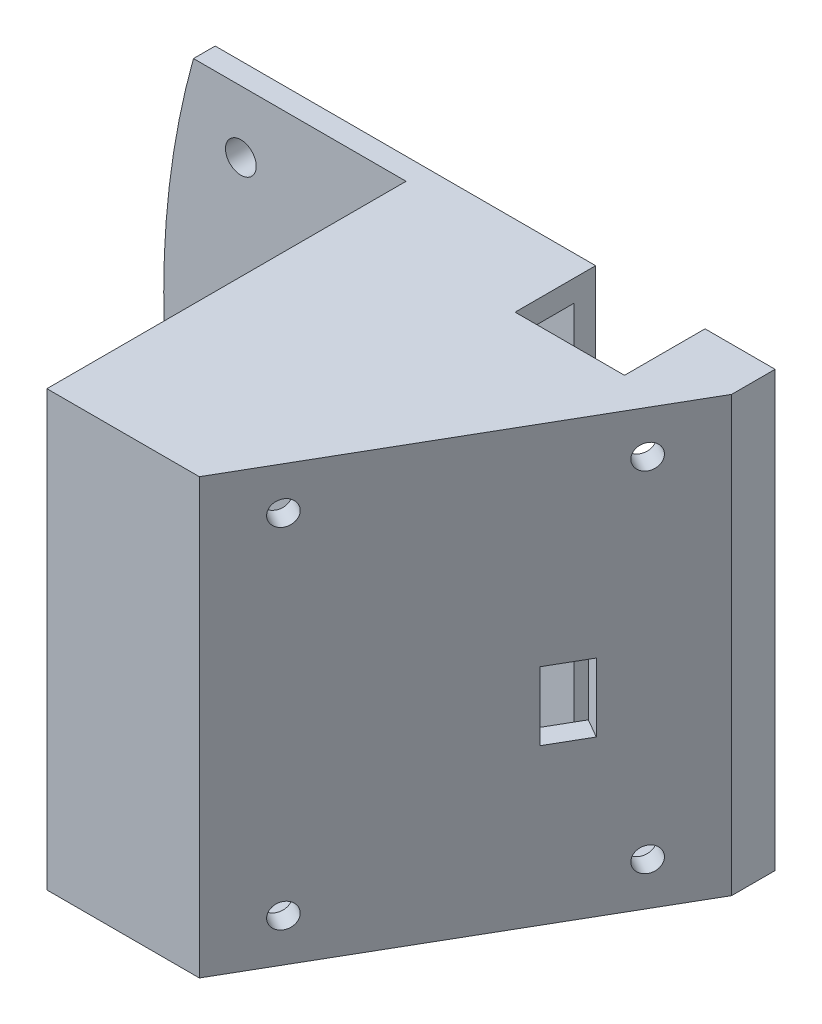
SolidWorks part; units mm, degrees
ref_plane "Front Plane" through (0, 0, 0) normal (0, 0, 1) x (1, 0, 0)
ref_plane "Top Plane" through (0, 0, 0) normal (0, 1, 0) x (1, 0, 0)
ref_plane "Right Plane" through (0, 0, 0) normal (1, 0, 0) x (0, 0, -1)
sketch "Sketch1" plane through (0, 0, 0) normal (0, 0, 1) x (1, 0, 0)
  line L0 (-113.6478, 31.75) -> (-31.75, 31.75)
  line L1 (-31.75, 31.75) -> (-31.75, -31.75)
  line L2 (-31.75, -31.75) -> (-113.6478, -31.75)
  circle A0 centre (-106.7159, 22.6832) radius 2.2479 construction
  circle A1 centre (-109.1, 0) radius 2.2479 construction
  circle A2 centre (-106.7159, -22.6832) radius 2.2479 construction
  circle A3 centre (-106.7159, 22.6832) radius 2.2479
  circle A4 centre (-109.1, 0) radius 2.2479
  circle A5 centre (-106.7159, -22.6832) radius 2.2479
  arc A6 (69.85, 95.1045) -> (69.85, -95.1045) centre (0, 0) ccw construction
  arc A7 (69.85, 95.1045) -> (69.85, -95.1045) centre (0, 0) ccw
  dimension "D1" = 31.75
  dimension "D4" = 63.5
sketch "Sketch5" plane through (0, 0, 0) normal (0, 1, 0) x (1, 0, 0)
  line L2 (-31.75, 0) -> (-31.75, -6.35)
  line L3 (-31.75, -6.35) -> (-60.25, -55.7134)
  line L4 (-60.25, -55.7134) -> (-82.55, -55.7134)
  line L5 (-82.55, -55.7134) -> (-82.55, 0)
  line L6 (-31.75, 0) -> (-82.55, 0)
  dimension "D1" = 6.35
  dimension "D2" = 57
  dimension "D3" = 50.8
  dimension "D4" = 60
ref_plane "Plane1" through (-21.0629, 0, -12.1607) normal (-0.866, 0, -0.5) x (-0.5, 0, 0.866)
sketch "Sketch6" plane through (-21.0629, 0, -12.1607) normal (-0.866, 0, -0.5) x (-0.5, 0, 0.866)
  line L1 (78.3743, -31.75) -> (21.3743, -31.75)
  line L2 (78.3743, -31.75) -> (78.3743, 31.75)
  line L3 (78.3743, 31.75) -> (21.3743, 31.75)
  line L4 (21.3743, -31.75) -> (21.3743, 31.75)
  line L5 (78.3743, -31.75) -> (21.3743, 31.75) construction
  line L6 (78.3743, 31.75) -> (21.3743, -31.75) construction
  line L7 (30.3743, 25.5) -> (69.3743, 25.5) construction
  line L8 (30.3743, 25.5) -> (30.3743, -25.5) construction
  line L9 (30.3743, -25.5) -> (69.3743, -25.5) construction
  line L10 (69.3743, 25.5) -> (69.3743, -25.5) construction
  line L11 (30.3743, 25.5) -> (69.3743, -25.5) construction
  line L12 (30.3743, -25.5) -> (69.3743, 25.5) construction
  point P0 (49.8743, 0)
  point P9 (49.8743, 0)
  dimension "D1" = 51
  dimension "D2" = 39
extrude "Boss-Extrude5" add sketch "Sketch5" along normal up to vertex (31.75 mm away) and the other way up to vertex (31.75 mm away) up to point (-60.25, 31.75, 55.7134) other way up to point (-60.25, -31.75, 55.7134)
extrude "Boss-Extrude6" add sketch "Sketch1" along normal blind 3.175 contours L0 A7 L2 L1 A3 A4 A5 region at (-73.8673, 0, 0)
shell "Shell2" thickness 3.175 removed face at (-82.55, 0, 29.4442)
hole_wizard "Ø1.0mm Dowel Hole1" positions "3DSketch1" profile "Sketch8" hole size "Ø1.0" standard "ANSI Metric"
sketch3d "3DSketch1"
  point P0 (-55.75, -25.5, 47.9192)
  point P2 (-55.75, 25.5, 47.9192)
  point P4 (-36.25, 25.5, 14.1442)
  point P6 (-36.25, -25.5, 14.1442)
sketch "Sketch8" plane through (-55.75, -25.5, 47.9192) normal (0, 1, 0) x (0.5, 0, -0.866)
  line L0 (0, 0) -> (0, 4.2565)
  line L1 (0, 4.2565) -> (1.8, 3.175)
  line L2 (1.8, 3.175) -> (1.8, 0)
  line L5 (1.8, 0) -> (0, 0)
  line L10 (0, 4.2565) -> (-1.8, 3.175) construction
  line L11 (0, -6.35) -> (0, 107.95) construction
  dimension "Hole Dia." = 3.6
  dimension "Hole Depth" = 3.175
  dimension "Drill Angle" = 118
sketch "Sketch9" plane through (0, -31.75, 0) normal (0, -1, 0) x (1, 0, 0)
  line L0 (69.85, 0) -> (-117.9995, 0) construction
  line L1 (-58, 11.7785) -> (-42, 11.7785)
  line L2 (-42, 9.25) -> (-58, 9.25) construction
  line L3 (-42, 9.25) -> (-58, 9.25) construction
  line L9 (-58, 11.7785) -> (-58, 0)
  line L10 (-58, 0) -> (-42, 0)
  line L11 (-42, 11.7785) -> (-42, 0)
  line M8 (-113.6478, 0) -> (-31.75, 0)
  dimension "D1" = 2.5285
extrude "Cut-Extrude1" cut sketch "Sketch9" against normal through all contours L11 L3 L9 M8 | L3 L11 L1 L9 region at (-50, -31.75, 10.5142) region at (-50, -31.75, 4.625)
sketch "Sketch10" plane through (-21.0629, 0, -12.1607) normal (-0.866, 0, -0.5) x (-0.5, 0, 0.866)
  line L0 (35.8743, 1) -> (41.8743, 1)
  line L1 (35.8743, 1) -> (35.8743, -9)
  line L2 (35.8743, -9) -> (41.8743, -9)
  line L3 (41.8743, 1) -> (41.8743, -9)
  dimension "D1" = 10
  dimension "D2" = 6
  dimension "D3" = 16.5
  dimension "D4" = 11.5
extrude "Cut-Extrude2" cut sketch "Sketch10" along normal up to surface (3.175 mm away) up to face at (-39.8996, 25.5, 14.1156)
